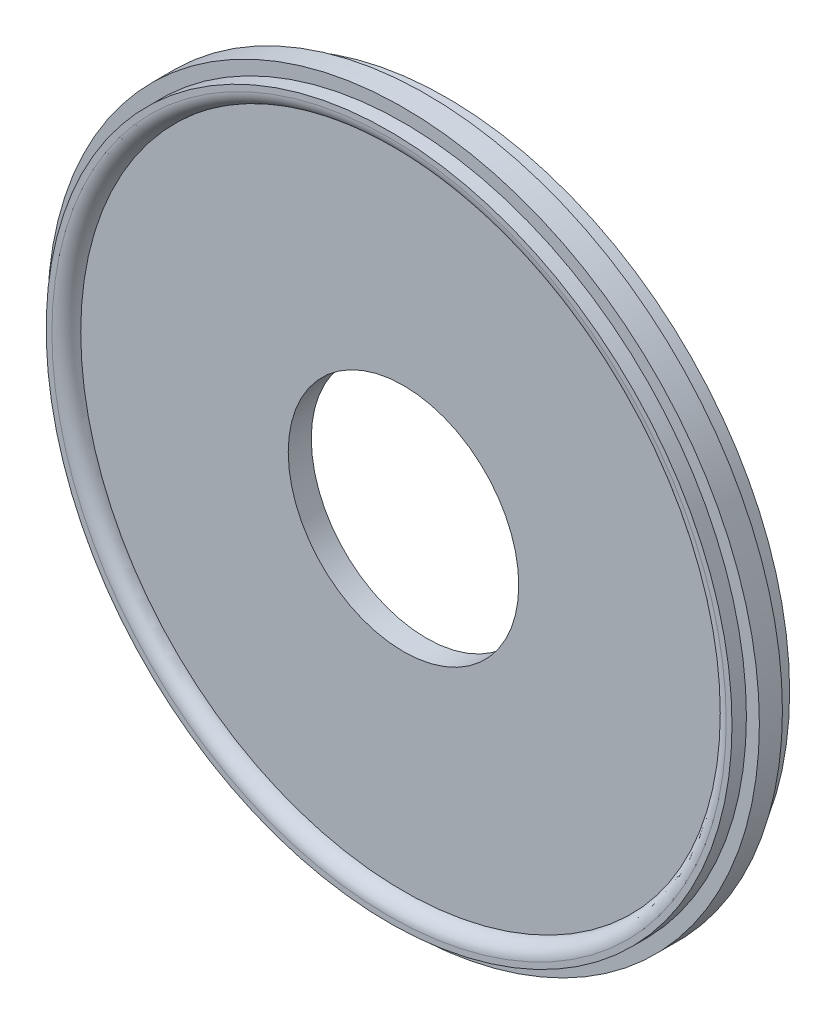
SolidWorks part; units mm, degrees
ref_plane "Ön Düzlem" through (0, 0, 0) normal (0, 0, 1) x (1, 0, 0)
ref_plane "Üst Düzlem" through (0, 0, 0) normal (0, 1, 0) x (1, 0, 0)
ref_plane "Sağ Düzlem" through (0, 0, 0) normal (1, 0, 0) x (0, 0, -1)
sketch "Sketch1" plane through (0, 0, 0) normal (0, 0, 1) x (1, 0, 0)
  circle A0 centre (0, 0) radius 59.5
  circle A1 centre (0, 0) radius 52
extrude "Boss-Extrude1" add sketch "Sketch1" along normal blind 3.5
sketch "Sketch2" plane through (0, 0, 3.5) normal (0, 0, 1) x (1, 0, 0)
  circle A0 centre (0, 0) radius 61.75
extrude "Boss-Extrude2" add sketch "Sketch2" along normal blind 4
sketch "Sketch3" plane through (0, 0, 7.5) normal (0, 0, 1) x (1, 0, 0)
  circle A0 centre (0, 0) radius 59.5
  circle A1 centre (0, 0) radius 56
extrude "Boss-Extrude3" add sketch "Sketch3" along normal blind 2.5
fillet "Fillet1" radius 2.5 1 edges at (56, 0, 10)
sketch "Sketch4" plane through (0, 0, 7.5) normal (0, 0, 1) x (1, 0, 0)
  circle A0 centre (0, 0) radius 20
extrude "Cut-Extrude1" cut sketch "Sketch4" against normal blind 22.5
